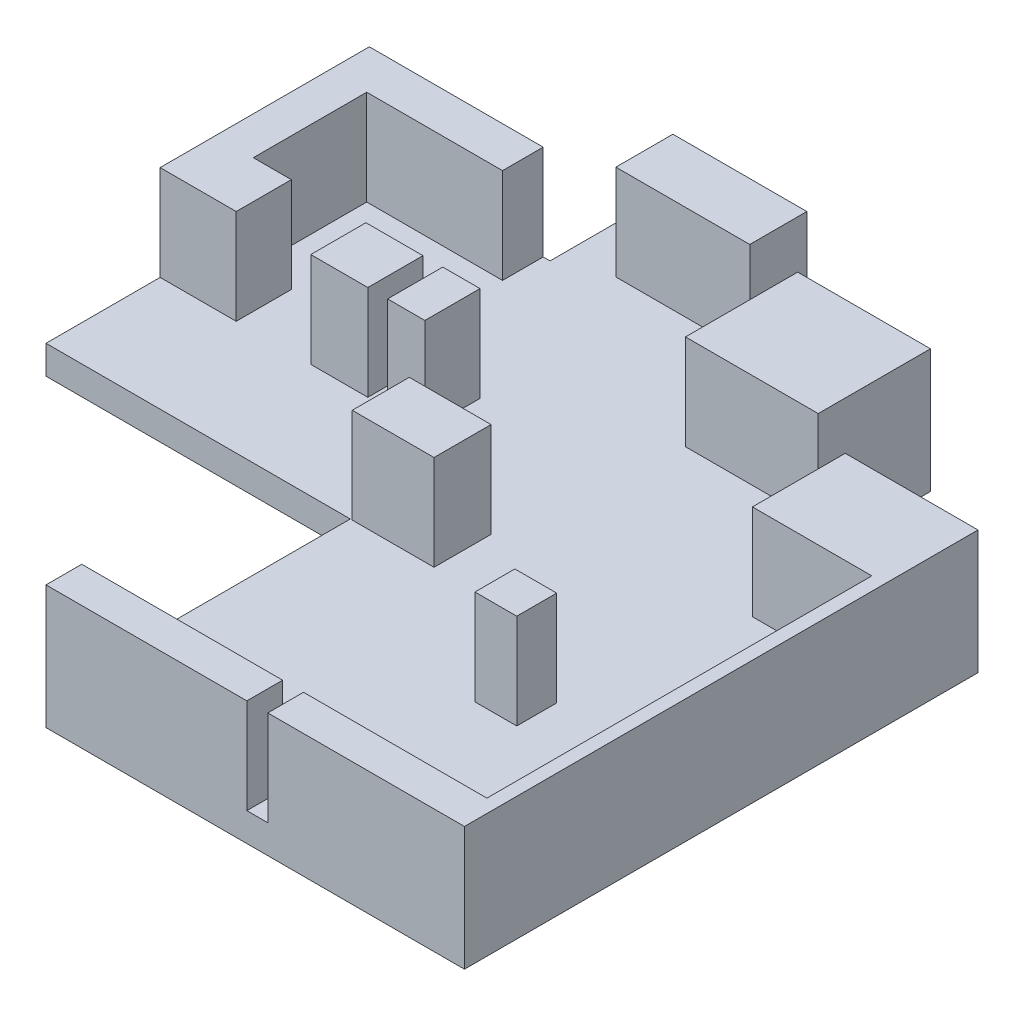
SolidWorks part; units mm, degrees
ref_plane "Front Plane" through (0, 0, 0) normal (0, 0, 1) x (1, 0, 0)
ref_plane "Top Plane" through (0, 0, 0) normal (0, 1, 0) x (1, 0, 0)
ref_plane "Right Plane" through (0, 0, 0) normal (1, 0, 0) x (0, 0, -1)
sketch "Sketch1" plane through (0, 0, 0) normal (0, 1, 0) x (1, 0, 0)
  line L1 (40, 0) -> (95, 0)
  line L2 (0, 40) -> (0, 85)
  line L3 (23.75, 95) -> (47.5, 95)
  line L4 (95, 0) -> (95, 70)
  line L7 (0, 85) -> (23.75, 85)
  line L8 (23.75, 95) -> (23.75, 85)
  line L10 (47.5, 95) -> (47.5, 87.5)
  line L14 (71.25, 87.5) -> (71.25, 70)
  line L15 (71.25, 70) -> (95, 70)
  line L17 (47.5, 87.5) -> (71.25, 87.5)
  line L21 (0, 40) -> (40, 40)
  line L22 (40, 0) -> (40, 40)
  dimension "D1" = 23.75
  dimension "D2" = 40
  dimension "D3" = 70
  dimension "D4" = 85
  dimension "D5" = 87.5
  dimension "D6" = 95
extrude "Boss-Extrude1" add sketch "Sketch1" along normal blind 3.75
sketch "Sketch2" plane through (0, 3.75, 0) normal (0, 1, 0) x (1, 0, 0)
  line L0 (53.55, 43.75) -> (53.55, 74.15) construction
  line L1 (95, 70) -> (77.3, 70)
  line L2 (95, 70) -> (95, 55.2)
  line L3 (95, 55.2) -> (77.3, 55.2)
  line L4 (77.3, 70) -> (77.3, 55.2)
  line L5 (71.25, 87.5) -> (53.55, 87.5)
  line L6 (71.25, 87.5) -> (71.25, 70)
  line L7 (71.25, 70) -> (53.55, 70)
  line L8 (53.55, 87.5) -> (53.55, 70)
  line L9 (53.55, 70.2) -> (53.55, 69.35) construction
  line L10 (19.8, 62.5) -> (27.3, 62.5)
  line L11 (47.5, 95) -> (29.8, 95)
  line L12 (47.5, 95) -> (47.5, 85)
  line L13 (47.5, 85) -> (29.8, 85)
  line L14 (29.8, 95) -> (29.8, 85)
  line L15 (40, 0) -> (66.4, 0)
  line L16 (40, 0) -> (40, 4.8)
  line L17 (40, 4.8) -> (66.4, 4.8)
  line L18 (66.4, 0) -> (66.4, 4.8)
  line L19 (40, 40) -> (51, 40)
  line L20 (40, 40) -> (40, 47.5)
  line L21 (40, 47.5) -> (51, 47.5)
  line L22 (51, 40) -> (51, 47.5)
  line L24 (27.3, 58.55) -> (27.3, 63.35) construction
  line L25 (0, 40) -> (10, 40)
  line L26 (0, 40) -> (0, 62.5)
  line L27 (0, 62.5) -> (10, 62.5)
  line L28 (27.3, 40) -> (27.3, 62.5)
  line L29 (23.1, 84.15) -> (23.1, 70.162) construction
  line L38 (0, 85) -> (23.1, 85)
  line L39 (29.8, 58.55) -> (29.8, 88.95) construction
  line L40 (95, 0) -> (68.9, 0)
  line L41 (95, 0) -> (95, 4.8)
  line L42 (95, 4.8) -> (68.9, 4.8)
  line L43 (68.9, 0) -> (68.9, 4.8)
  line L44 (29.8, 62.5) -> (34.8, 62.5)
  line L45 (29.8, 62.5) -> (29.8, 40)
  line L46 (29.8, 40) -> (34.8, 40)
  line L47 (34.8, 62.5) -> (34.8, 40)
  line L48 (29.8, 63.35) -> (29.8, 62.5) construction
  line L49 (0, 40) -> (40, 40) construction
  line L50 (0, 85) -> (0, 77.156)
  line L55 (95, 70) -> (71.25, 70) construction
  line L60 (0, 77.156) -> (23.1, 77.156)
  line L61 (23.1, 85) -> (23.1, 77.156)
  line L62 (95, 0) -> (95, 70) construction
  line L68 (10, 62.5) -> (10, 40)
  line L70 (74.5, 32.625) -> (69, 32.625)
  line L71 (74.5, 32.625) -> (74.5, 27.375)
  line L72 (74.5, 27.375) -> (69, 27.375)
  line L73 (69, 32.625) -> (69, 27.375)
  line L74 (19.8, 62.5) -> (19.8, 40)
  line L75 (19.8, 40) -> (27.3, 40)
  point P47 (71.75, 27.375)
  dimension "D1" = 5
  dimension "D2" = 5.5
  dimension "D3" = 5.25
  dimension "D4" = 20.5
  dimension "D5" = 27.375
  dimension "D6" = 11
  dimension "D7" = 7.5
  dimension "D8" = 22.5
  dimension "D9" = 10
  dimension "D10" = 7.5
extrude "Boss-Extrude2" add sketch "Sketch2" along normal blind 12.5
sketch "Sketch5" plane through (0, 0, 0) normal (0, -1, 0) x (1, 0, 0)
  line L0 (71.25, -87.5) -> (47.5, -87.5) construction
  line L1 (23.75, -85) -> (0, -85)
  line L2 (23.75, -85) -> (23.75, -82.5)
  line L3 (23.75, -82.5) -> (0, -82.5)
  line L4 (0, -85) -> (0, -82.5)
  line L5 (71.25, -87.5) -> (47.5, -87.5)
  line L6 (23.75, -95) -> (47.5, -95)
  line L7 (23.75, -95) -> (23.75, -92.5)
  line L8 (23.75, -92.5) -> (47.5, -92.5)
  line L9 (47.5, -95) -> (47.5, -92.5)
  line L10 (71.25, -87.5) -> (71.25, -85)
  line L15 (71.25, -85) -> (47.5, -85)
  line L16 (71.25, -70) -> (95, -70)
  line L17 (71.25, -70) -> (71.25, -67.5)
  line L18 (71.25, -67.5) -> (95, -67.5)
  line L19 (95, -70) -> (95, -67.5)
  line L20 (0, -85) -> (0, -40) construction
  line L21 (23.75, -85) -> (0, -85) construction
  line L22 (47.5, -87.5) -> (47.5, -85)
  line L23 (71.25, -70) -> (71.25, -87.5) construction
  line L24 (95, 0) -> (95, -70) construction
  dimension "D1" = 23.75
  dimension "D2" = 2.5
  dimension "D3" = 15
  dimension "D4" = 7.5
extrude "Cut-Extrude2" cut sketch "Sketch5" against normal through all
sketch "Sketch6" plane through (0, 0, 0) normal (0, -1, 0) x (1, 0, 0)
  line L0 (0, -82.5) -> (12.5, -82.5) construction
  line L1 (59.15, -87.9) -> (57.5, -87.9)
  line L2 (23.75, -82.5) -> (0, -82.5) construction
  line L3 (12.5, -82.5) -> (12.5, -86.25) construction
  line L4 (37.1, -95.4) -> (38.75, -95.4)
  line L5 (23.75, -92.5) -> (36.25, -92.5) construction
  line L6 (47.5, -92.5) -> (23.75, -92.5) construction
  line L7 (13.35, -85.4) -> (15, -85.4)
  line L11 (47.5, -85) -> (60, -85) construction
  line L13 (71.25, -85) -> (47.5, -85) construction
  line L15 (36.25, -92.5) -> (36.25, -96.25) construction
  line L16 (71.25, -67.5) -> (83.75, -67.5) construction
  line L19 (95, -67.5) -> (71.25, -67.5) construction
  line L25 (60, -85) -> (60, -88.75) construction
  line L44 (83.75, -67.5) -> (83.75, -71.25) construction
  line L46 (81.25, -71.25) -> (86.25, -71.25) construction
  line L47 (81.25, -70.4) -> (82.9, -70.4)
  line L48 (81.25, -72.1) -> (86.25, -72.1)
  line L49 (62.5, -88.75) -> (57.5, -88.75) construction
  line L50 (62.5, -89.6) -> (57.5, -89.6)
  line L51 (62.5, -87.9) -> (60.85, -87.9)
  line L52 (33.75, -96.25) -> (38.75, -96.25) construction
  line L53 (33.75, -95.4) -> (35.4, -95.4)
  line L54 (33.75, -97.1) -> (38.75, -97.1)
  line L55 (10, -86.25) -> (15, -86.25) construction
  line L56 (10, -85.4) -> (11.65, -85.4)
  line L57 (10, -87.1) -> (15, -87.1)
  line L58 (83.75, -71.25) -> (83.75, -67.5) construction
  line L59 (82.9, -70.4) -> (82.9, -67.5)
  line L60 (84.6, -70.4) -> (84.6, -67.5)
  line L61 (60, -85) -> (60, -88.75) construction
  line L62 (60.85, -85) -> (60.85, -87.9)
  line L63 (59.15, -85) -> (59.15, -87.9)
  line L64 (36.25, -96.25) -> (36.25, -92.5) construction
  line L65 (35.4, -95.4) -> (35.4, -92.5)
  line L66 (37.1, -95.4) -> (37.1, -92.5)
  line L67 (12.5, -82.5) -> (12.5, -86.25) construction
  line L68 (13.35, -82.5) -> (13.35, -85.4)
  line L69 (11.65, -82.5) -> (11.65, -85.4)
  line L70 (84.6, -70.4) -> (86.25, -70.4)
  arc A16 (81.25, -70.4) -> (81.25, -72.1) centre (81.25, -71.25) ccw
  arc A17 (86.25, -72.1) -> (86.25, -70.4) centre (86.25, -71.25) ccw
  arc A18 (62.5, -89.6) -> (62.5, -87.9) centre (62.5, -88.75) ccw
  arc A19 (57.5, -87.9) -> (57.5, -89.6) centre (57.5, -88.75) ccw
  arc A20 (33.75, -95.4) -> (33.75, -97.1) centre (33.75, -96.25) ccw
  arc A21 (38.75, -97.1) -> (38.75, -95.4) centre (38.75, -96.25) ccw
  arc A22 (10, -85.4) -> (10, -87.1) centre (10, -86.25) ccw
  arc A23 (15, -87.1) -> (15, -85.4) centre (15, -86.25) ccw
  arc A25 (84.6, -67.5) -> (82.9, -67.5) centre (83.75, -67.5) ccw
  arc A26 (60.85, -85) -> (59.15, -85) centre (60, -85) ccw
  arc A29 (37.1, -92.5) -> (35.4, -92.5) centre (36.25, -92.5) ccw
  arc A30 (13.35, -82.5) -> (11.65, -82.5) centre (12.5, -82.5) ccw
  point P24 (83.75, -71.25)
  point P27 (12.5, -86.25)
  point P30 (36.25, -96.25)
  point P33 (60, -88.75)
  point P36 (83.75, -71.25)
  point P41 (60, -88.75)
  point P46 (36.25, -96.25)
  point P51 (12.5, -86.25)
  point P56 (83.75, -69.375)
  point P61 (60, -86.875)
  point P66 (36.25, -94.375)
  point P71 (12.5, -84.375)
  dimension "D4" = 0.85
  dimension "D1" = 12.5
  dimension "D2" = 3.75
  dimension "D3" = 5
extrude "Boss-Extrude3" add sketch "Sketch6" against normal blind 15
chamfer "Chamfer1" distance 3.75 angle 45 7 edges at (10.825, 15, -85.4) (34.575, 15, -95.4) (60, 15, -89.6) (82.075, 15, -70.4) (12.5, 15, -87.1) (36.25, 15, -97.1) (83.75, 15, -72.1)
sketch "Sketch7" plane through (0, 16.25, 0) normal (0, 1, 0) x (1, 0, 0)
  line L0 (0, 77.156) -> (23.1, 77.156) construction
  line L1 (23.1, 82.5) -> (22.85, 82.5)
  line L2 (23.1, 82.5) -> (23.1, 77.156)
  line L3 (23.1, 77.156) -> (22.85, 77.156)
  line L4 (22.85, 82.5) -> (22.85, 77.156)
  line L5 (29.8, 85) -> (47.5, 85) construction
  line L6 (29.8, 92.5) -> (29.9, 92.5)
  line L7 (29.8, 92.5) -> (29.8, 85)
  line L8 (29.8, 85) -> (29.9, 85)
  line L9 (29.9, 92.5) -> (29.9, 85)
  line L10 (53.55, 85) -> (53.55, 70) construction
  line L11 (29.8, 62.5) -> (29.9, 62.5)
  line L12 (29.8, 62.5) -> (29.8, 55)
  line L14 (29.9, 62.5) -> (29.9, 55)
  line L15 (53.55, 70) -> (71.25, 70) construction
  line L16 (53.55, 85) -> (53.8, 85)
  line L17 (53.55, 85) -> (53.55, 70)
  line L18 (53.55, 70) -> (53.8, 70)
  line L19 (53.8, 85) -> (53.8, 70)
  line L20 (40, 40) -> (51, 40) construction
  line L21 (40, 47.5) -> (40.25, 47.5)
  line L22 (40, 47.5) -> (40, 40)
  line L23 (40, 40) -> (40.25, 40)
  line L24 (40.25, 47.5) -> (40.25, 40)
  line L25 (77.3, 55.2) -> (95, 55.2) construction
  line L30 (34.8, 40) -> (34.8, 62.5) construction
  line L32 (0, 40) -> (0, 55)
  line L33 (0, 55) -> (29.8, 55)
  line L34 (34.8, 40) -> (34.8, 55)
  line L35 (29.9, 55) -> (34.8, 55)
  line L36 (0, 40) -> (34.8, 40)
  line L37 (77.3, 67.5) -> (77.55, 67.5)
  line L38 (71.25, 85) -> (53.55, 85) construction
  line L39 (0, 62.5) -> (0, 40) construction
  line L40 (0, 40) -> (10, 40) construction
  line L41 (77.3, 67.5) -> (77.3, 55.2)
  line L42 (77.3, 55.2) -> (77.55, 55.2)
  line L43 (77.55, 67.5) -> (77.55, 55.2)
  line L45 (68.9, 4.8) -> (69.15, 4.8)
  line L46 (68.9, 4.8) -> (68.9, 0)
  line L47 (68.9, 0) -> (69.15, 0)
  line L48 (69.15, 4.8) -> (69.15, 0)
  dimension "D1" = 0.1
  dimension "D2" = 15
  dimension "D3" = 0.1
  dimension "D4" = 0.25
extrude "Cut-Extrude3" cut sketch "Sketch7" against normal up to surface (12.5 mm away) and the other way through all up to face at (42.4595, 3.75, -52.8084)
sketch "Sketch8" [suppressed] plane through (0, 3.75, 0) normal (0, 1, 0) x (1, 0, 0)
  line L1 (0, 82.5) -> (23.75, 82.5)
  line L2 (0, 82.5) -> (0, 77.5)
  line L5 (23.75, 92.5) -> (47.5, 92.5)
  line L7 (26.25, 87.5) -> (45, 87.5)
  line L10 (47.5, 82.5) -> (71.25, 82.5)
  line L14 (95, 0) -> (95, 67.5) construction
  line L15 (71.25, 67.5) -> (95, 67.5)
  line L18 (95, 67.5) -> (95, 62.5)
  line L20 (0, 77.5) -> (26.25, 77.5)
  line L24 (26.25, 87.5) -> (26.25, 77.5)
  line L28 (45, 87.5) -> (45, 77.5)
  line L32 (68.75, 77.5) -> (68.75, 62.5)
  line L33 (45, 77.5) -> (68.75, 77.5)
  line L34 (47.5, 92.5) -> (47.5, 82.5)
  line L35 (23.75, 92.5) -> (23.75, 82.5)
  line L36 (68.75, 62.5) -> (95, 62.5)
  line L37 (71.25, 67.5) -> (71.25, 82.5)
  point P1 (71.25, 75)
  dimension "D1" = 5
  dimension "D2" = 2.5
  dimension "D3" = 2.5
  dimension "D4" = 2.5
  dimension "D5" = 10
  dimension "D6" = 15
extrude "Boss-Extrude4" [suppressed] add sketch "Sketch8" along normal up to surface (8.75 mm away)
chamfer "Chamfer2" [suppressed] distance 5 angle 60
sketch "Sketch9" plane through (0, 16.25, 0) normal (0, 1, 0) x (1, 0, 0)
  line L0 (95, 55.2) -> (95, 67.5) construction
  line L1 (77.55, 55.2) -> (95, 55.2)
  line L2 (77.55, 55.2) -> (77.55, 55.3)
  line L3 (77.55, 55.3) -> (95, 55.3)
  line L4 (95, 55.2) -> (95, 55.3)
  line L5 (71.25, 70) -> (71.25, 85) construction
  line L6 (53.8, 70) -> (71.25, 70)
  line L7 (53.8, 70) -> (53.8, 70.25)
  line L8 (53.8, 70.25) -> (71.25, 70.25)
  line L9 (71.25, 70) -> (71.25, 70.25)
  line L10 (0, 62.5) -> (0, 55) construction
  line L11 (34.8, 62.5) -> (0, 62.5)
  line L12 (34.8, 62.5) -> (34.8, 62.25)
  line L13 (34.8, 62.25) -> (0, 62.25)
  line L14 (0, 62.5) -> (0, 62.25)
  line L15 (95, 0) -> (95, 4.8) construction
  line L16 (40, 4.8) -> (95, 4.8)
  line L17 (40, 4.8) -> (40, 4.7)
  line L18 (40, 4.7) -> (95, 4.7)
  line L19 (95, 4.8) -> (95, 4.7)
  dimension "D1" = 0.1
  dimension "D2" = 0.25
  dimension "D3" = 0.1
extrude "Cut-Extrude4" cut sketch "Sketch9" against normal up to surface (12.5 mm away) and the other way through all up to face at (23.55, 3.75, -58.75)
sketch "Sketch10" plane through (0, 3.75, 0) normal (0, 1, 0) x (1, 0, 0)
  line L0 (69.15, 4.7) -> (95, 4.7) construction
  line L1 (95, 55.3) -> (93.25, 55.3)
  line L2 (95, 55.3) -> (95, 4.7)
  line L3 (95, 4.7) -> (93.25, 4.7)
  line L4 (93.25, 55.3) -> (93.25, 4.7)
  line L5 (0, 62.25) -> (10, 62.25) construction
  line L6 (0, 77.156) -> (5, 77.156)
  line L7 (0, 77.156) -> (0, 62.25)
  line L8 (0, 62.25) -> (5, 62.25)
  line L9 (5, 77.156) -> (5, 62.25)
  dimension "D1" = 1.75
  dimension "D2" = 5
extrude "Boss-Extrude5" add sketch "Sketch10" along normal up to surface (12.5 mm away) up to face at (11.425, 16.25, -79.828)
